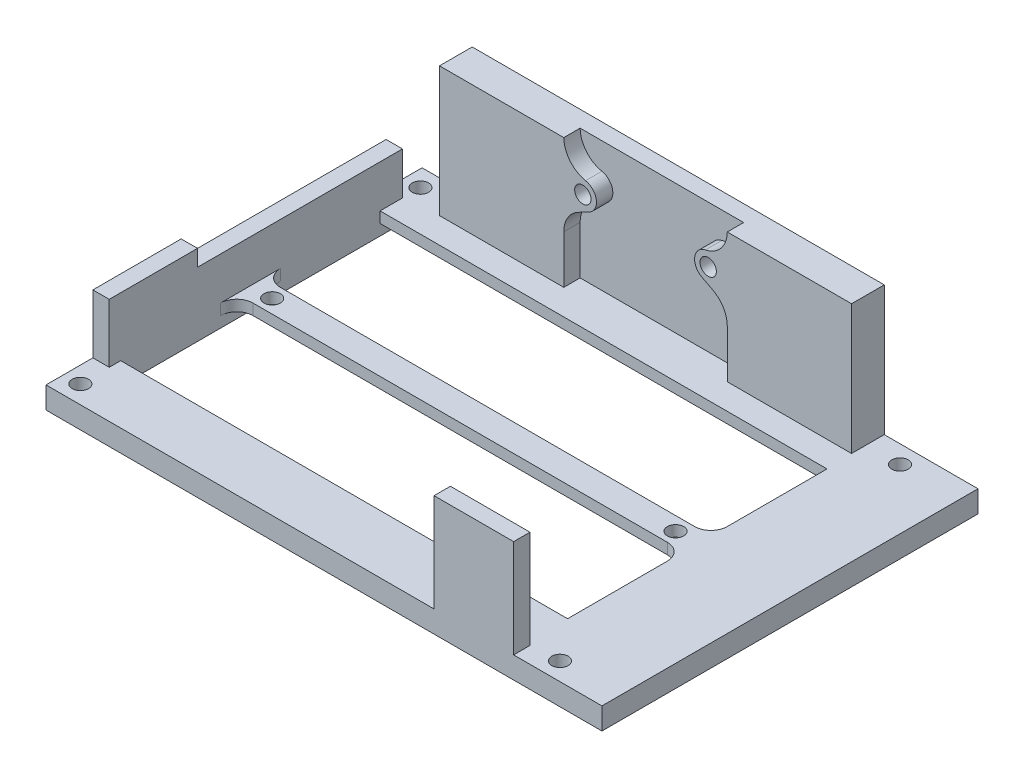
SolidWorks part; units mm, degrees
ref_plane "Front" through (0, 0, 0) normal (0, 0, 1) x (1, 0, 0)
ref_plane "Top" through (0, 0, 0) normal (0, 1, 0) x (1, 0, 0)
ref_plane "Right" through (0, 0, 0) normal (1, 0, 0) x (0, 0, -1)
sketch "Sketch1" plane through (0, 0, 0) normal (0, 1, 0) x (1, 0, 0)
  line L0 (51, 34.5) -> (-51, -34.5) construction
  line L1 (-51, 34.5) -> (51, 34.5)
  line L2 (-51, 34.5) -> (-51, -34.5)
  line L3 (-51, -34.5) -> (51, -34.5)
  line L4 (51, 34.5) -> (51, -34.5)
  line L5 (-48, 0) -> (-51, 0) construction
  line L6 (-48, 25.8) -> (34, 25.8)
  line L7 (-48, 25.8) -> (-48, -25.8)
  line L8 (-48, -25.8) -> (34, -25.8)
  line L9 (34, 25.8) -> (34, -25.8)
  line L11 (-48, 31.2) -> (40, 31.2) construction
  line L12 (-48, 31.2) -> (-48, -31.2) construction
  line L13 (-48, -31.2) -> (40, -31.2) construction
  line L14 (40, 31.2) -> (40, -31.2) construction
  circle A0 centre (-48, 31.2) radius 1.5
  circle A1 centre (40, 31.2) radius 1.5
  circle A2 centre (40, -31.2) radius 1.5
  circle A3 centre (-48, -31.2) radius 1.5
  dimension "D5" = 3
  dimension "D1" = 69
  dimension "D2" = 102
  dimension "D3" = 51.6
  dimension "D4" = 82
  dimension "D6" = 88
  dimension "D7" = 62.4
  dimension "D8" = 3
extrude "Boss-Extrude1" add sketch "Sketch1" along normal blind 2
sketch "Sketch2" plane through (0, 2, 0) normal (0, 1, 0) x (1, 0, 0)
  line L0 (34, -25.8) -> (34, 25.8) construction
  line L1 (51, -34.5) -> (-51, -34.5)
  line L2 (51, -34.5) -> (51, 34.5)
  line L3 (51, 34.5) -> (-51, 34.5)
  line L4 (-51, -34.5) -> (-51, 34.5)
  line L5 (-48, 23.8) -> (34, 23.8)
  line L6 (-48, 23.8) -> (-48, 2.5)
  line L7 (-48, 2.5) -> (34, 2.5)
  line L8 (34, 23.8) -> (34, 2.5)
  line L9 (-51, 0) -> (51, 0) construction
  line L10 (34, -2.5) -> (-48, -2.5)
  line L11 (34, -2.5) -> (34, -23.8)
  line L12 (34, -23.8) -> (-48, -23.8)
  line L13 (-48, -2.5) -> (-48, -23.8)
  line L14 (-7, 23.8) -> (-7, -23.8) construction
  line L15 (-48, -25.8) -> (34, -25.8) construction
  line L16 (-48, 25.8) -> (-48, -25.8) construction
  circle A0 centre (-44, 0) radius 1.5
  circle A1 centre (30, 0) radius 1.5
  point P26 (0, 18.7574)
  point P27 (0, 0)
  dimension "D2" = 74
  dimension "D3" = 3
  dimension "D1" = 5
  dimension "D4" = 2
extrude "Boss-Extrude2" add sketch "Sketch2" along normal blind 2
fillet "Fillet1" radius 3 4 edges at (34, 3, -2.5) (34, 3, 2.5) (-48, 3, 2.5) (-48, 3, -2.5)
sketch "Sketch3" plane through (0, 2, 0) normal (0, -1, 0) x (1, 0, 0)
  circle A0 centre (-48, -31.2) radius 1.5 construction
  circle A1 centre (-48, 31.2) radius 1.5
  circle A2 centre (-48, 31.2) radius 1.5
  circle A3 centre (40, -31.2) radius 1.5 construction
  circle A4 centre (40, 31.2) radius 1.5 construction
  circle A5 centre (-48, -31.2) radius 1.5
  circle A6 centre (40, -31.2) radius 1.5
  circle A7 centre (40, 31.2) radius 1.5
  dimension "D1" = 0
extrude "Cut-Extrude1" cut sketch "Sketch3" against normal through all
sketch "Sketch9" plane through (0, 4, 0) normal (0, 1, 0) x (1, 0, 0)
  line L0 (51, 34.5) -> (-51, 34.5) construction
  line L1 (-41.8, 34.5) -> (33.8, 34.5)
  line L2 (-41.8, 34.5) -> (-41.8, 28.5)
  line L3 (-41.8, 28.5) -> (33.8, 28.5)
  line L4 (33.8, 34.5) -> (33.8, 28.5)
  line L5 (-51, 34.5) -> (-51, -34.5) construction
  dimension "D1" = 6
  dimension "D2" = 9.2
  dimension "D3" = 75.6
extrude "Boss-Extrude5" add sketch "Sketch9" along normal blind 23.8
sketch "Sketch10" plane through (0, 0, -28.5) normal (0, 0, 1) x (1, 0, 0)
  line L0 (-41.8, 27.8) -> (33.8, 27.8) construction
  line L1 (-19, 27.8) -> (11, 27.8)
  line L2 (-19, 27.8) -> (-19, 4)
  line L3 (-19, 4) -> (11, 4)
  line L4 (11, 27.8) -> (11, 4)
  line L5 (-4, 27.8) -> (-4, 4) construction
  line L6 (-41.8, 4) -> (33.8, 4) construction
  line L7 (-19, 5.5) -> (11, 5.5) construction
  line L8 (-15.5, 20.5) -> (7.5, 20.5) construction
  line L9 (-19, 15.9) -> (-14.3609, 18.2746)
  line L10 (11, 15.9) -> (6.3609, 18.2746)
  line L11 (-15.5, 23) -> (-19, 23)
  line L12 (7.5, 23) -> (11, 23)
  circle A0 centre (-15.5, 20.5) radius 1.5
  circle A1 centre (7.5, 20.5) radius 1.5
  arc A2 (-14.3609, 18.2746) -> (-15.5, 23) centre (-15.5, 20.5) ccw
  arc A3 (7.5, 23) -> (6.3609, 18.2746) centre (7.5, 20.5) ccw
  point P16 (-4, 20.5)
  line M9 (-41.8, 4) -> (33.8, 4)
  line M11 (33.8, 27.8) -> (-41.8, 27.8)
  dimension "D3" = 5
  dimension "D4" = 3
  dimension "D1" = 30
  dimension "D2" = 23
  dimension "D5" = 15
  dimension "D6" = 3
extrude "Cut-Extrude6" cut sketch "Sketch10" against normal blind 3 contours A3 L12 L4 L2 L11 A2 L9 L10 M11 M9 | A0 | A1 region at (-4, 15.495, -28.5) region at (-15.5, 20.5, -28.5) region at (7.5, 20.5, -28.5)
fillet "Fillet3" radius 5 4 edges at (-19, 15.9, -30) (11, 15.9, -30) (11, 23, -30) (-19, 23, -30)
sketch "Sketch11" plane through (0, 4, 0) normal (0, 1, 0) x (1, 0, 0)
  line L0 (-51, -34.5) -> (51, -34.5) construction
  line L1 (20.2, -34.5) -> (34.8, -34.5)
  line L2 (20.2, -34.5) -> (20.2, -31.5)
  line L3 (20.2, -31.5) -> (34.8, -31.5)
  line L4 (34.8, -34.5) -> (34.8, -31.5)
  line L5 (-51, 34.5) -> (-51, -34.5) construction
  dimension "D1" = 14.6
  dimension "D2" = 3
  dimension "D3" = 71.2
extrude "Boss-Extrude6" add sketch "Sketch11" along normal blind 18
sketch "Sketch12" plane through (0, 4, 0) normal (0, 1, 0) x (1, 0, 0)
  line L0 (-51, 34.5) -> (-51, -34.5) construction
  line L1 (-51, 27.9) -> (-48, 27.9)
  line L2 (-51, 27.9) -> (-51, -25.9)
  line L3 (-51, -25.9) -> (-48, -25.9)
  line L4 (-48, 27.9) -> (-48, -25.9)
  line L5 (-48, -5.5) -> (-48, -23.8) construction
  line L6 (-41.8, 34.5) -> (-51, 34.5) construction
  line L7 (-51, -34.5) -> (20.2, -34.5) construction
  dimension "D1" = 6.6
  dimension "D2" = 8.6
extrude "Boss-Extrude7" add sketch "Sketch12" along normal blind 7.8 contours L2 L3 L4 L1
sketch "Sketch13" plane through (0, 11.8, 0) normal (0, 1, 0) x (1, 0, 0)
  line L0 (-51, 27.9) -> (-51, -25.9) construction
  line L1 (-51, -9.7) -> (-48, -9.7)
  line L2 (-51, -9.7) -> (-51, -25.9)
  line L3 (-51, -25.9) -> (-48, -25.9)
  line L4 (-48, -9.7) -> (-48, -25.9)
  line L5 (-48, 27.9) -> (-48, -25.9) construction
  line L7 (-51, -25.9) -> (-48, -25.9) construction
  point P10 (-49.5, -25.9)
  dimension "D1" = 16.2
extrude "Boss-Extrude8" add sketch "Sketch13" along normal blind 3
